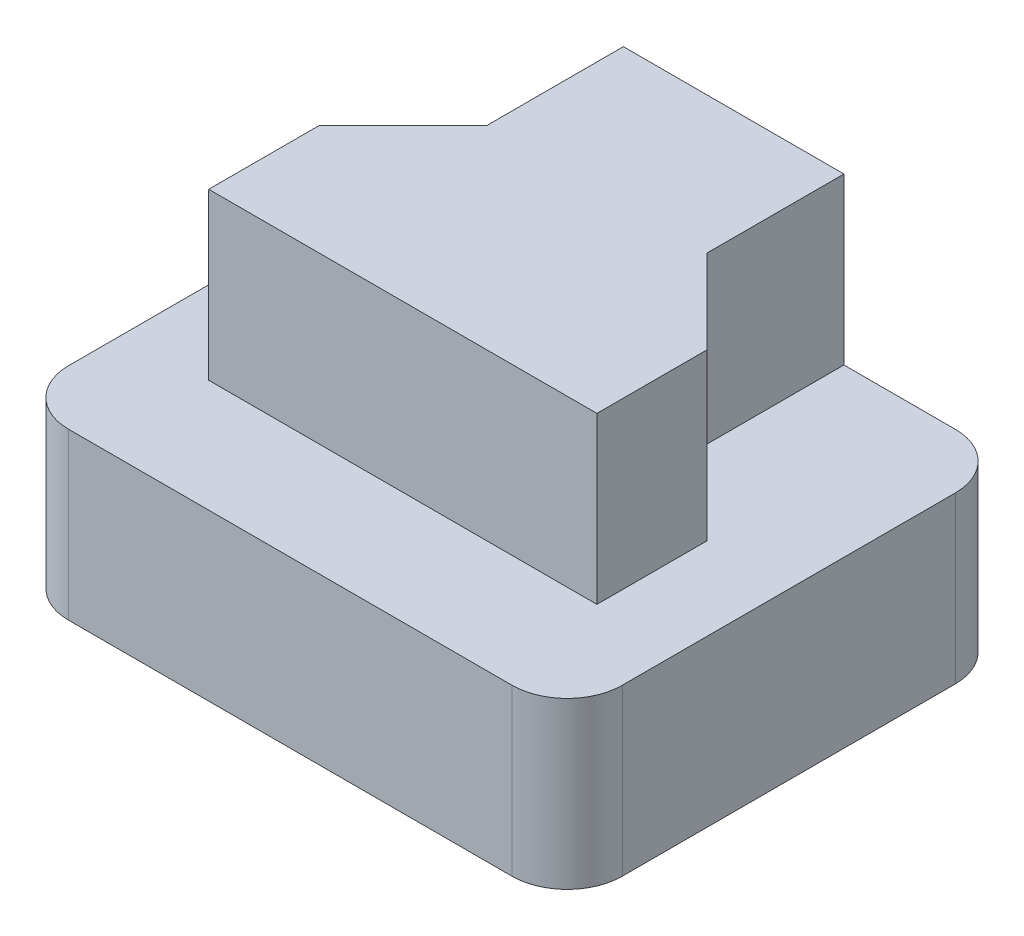
SolidWorks part; units mm, degrees
ref_plane "Front Plane" through (0, 0, 0) normal (0, 0, 1) x (1, 0, 0)
ref_plane "Top Plane" through (0, 0, 0) normal (0, 1, 0) x (1, 0, 0)
ref_plane "Right Plane" through (0, 0, 0) normal (1, 0, 0) x (0, 0, -1)
sketch "Sketch1" plane through (0, 0, 0) normal (0, 1, 0) x (1, 0, 0)
  line L0 (-2, 4.02) -> (2, 4.02)
  line L1 (5.02, 4.02) -> (-5.02, 4.02)
  line L2 (5.02, 4.02) -> (5.02, -4.02)
  line L3 (5.02, -4.02) -> (-5.02, -4.02)
  line L4 (-5.02, 4.02) -> (-5.02, -4.02)
  line L5 (0, -4.02) -> (0, 4.02) construction
  line L6 (5.02, 0) -> (-5.02, 0) construction
  line L7 (-7.02, 6.02) -> (7.02, 6.02)
  line L8 (-7.02, 6.02) -> (-7.02, -6.02)
  line L9 (-7.02, -6.02) -> (7.02, -6.02)
  line L10 (7.02, 6.02) -> (7.02, -6.02)
  line L11 (0, -6.02) -> (0, 6.02) construction
  line L12 (-7.02, 0) -> (7.02, 0) construction
  line L13 (2, 4.02) -> (2, 0.02)
  line L14 (2, 0.02) -> (3.52, 0.02)
  line L15 (3.52, 0.02) -> (3.52, -1.98)
  line L16 (3.52, -1.98) -> (-3.52, -1.98)
  line L17 (-3.52, -1.98) -> (-3.52, 0.02)
  line L18 (-3.52, 0.02) -> (-2, 0.02)
  line L19 (-2, 0.02) -> (-2, 4.02)
  line L20 (-3.52, 0.02) -> (-2, 1.54)
  line L21 (2, 1.54) -> (3.52, 0.02)
  point P0 (0, 0)
  point P4 (0, 0)
  point P19 (0, 4.02)
  point P23 (0, -1.98)
  dimension "D1" = 8.04
  dimension "D2" = 10.04
  dimension "D3" = 2
  dimension "D4" = 2
  dimension "D6" = 4
  dimension "D7" = 6
  dimension "D5" = 2
  dimension "D8" = 1.5
  dimension "D9" = 45
extrude "Boss-Extrude1" add sketch "Sketch1" along normal blind 3 contours L1 L4 L3 L2
extrude "Boss-Extrude2" add sketch "Sketch1<3>" along normal blind 3 from surface contours L19 L18 L17 L16 L15 L14 L13 L0 | L20 L18 L19 | L21 L13 L14 region at (0, 0, -0.6157) region at (-2.5067, 0, -0.5267) region at (2.5067, 0, -0.5267) starting at face at (0, 3, 0)
sketch "Sketch1<3>" plane through (0, 0, 0) normal (0, 1, 0) x (1, 0, 0) same geometry as "Sketch1"
fillet "Fillet2" radius 1 4 edges at (5.02, 1.5, 4.02) (-5.02, 1.5, 4.02) (-5.02, 1.5, -4.02) (5.02, 1.5, -4.02)
equation "\"LF\" = 0.04mm"
equation "\"TF\" = 0.02mm"
equation "\"AngLF\"= 0.5"
equation "\"AngTF\"= 0.3"
equation "\"D1@Sketch1\"=8+2*\"TF\""
